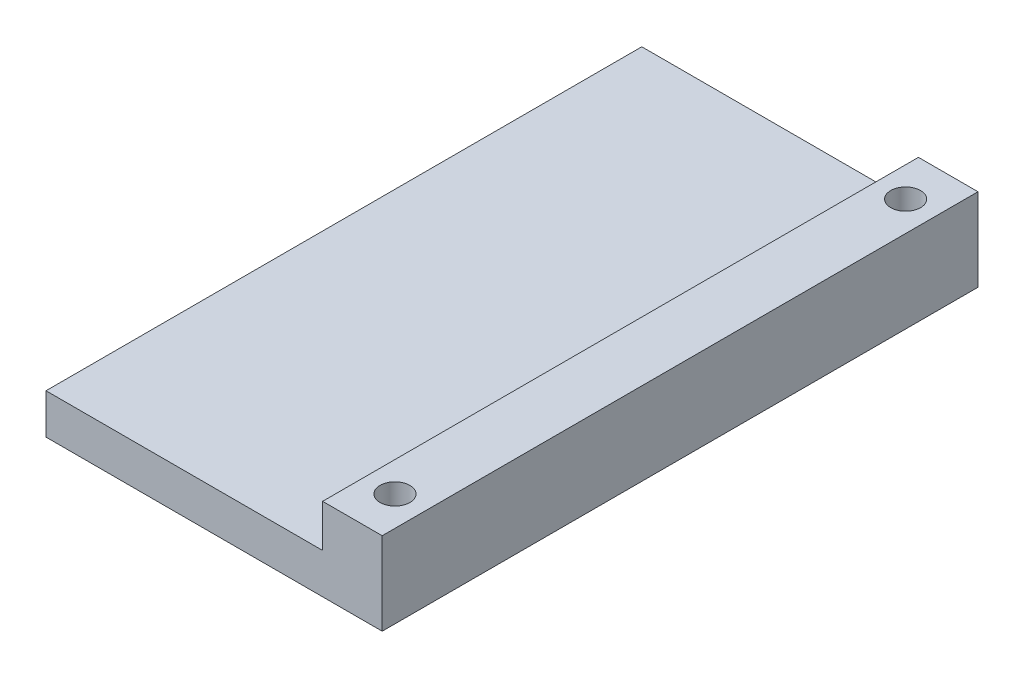
SolidWorks part; units mm, degrees
ref_plane "Front Plane" through (0, 0, 0) normal (0, 0, 1) x (1, 0, 0)
ref_plane "Top Plane" through (0, 0, 0) normal (0, 1, 0) x (1, 0, 0)
ref_plane "Right Plane" through (0, 0, 0) normal (1, 0, 0) x (0, 0, -1)
sketch "Sketch1" plane through (0, 0, 0) normal (0, 1, 0) x (1, 0, 0)
  line L1 (0, 0) -> (41.275, 0)
  line L2 (0, 0) -> (0, 88.9)
  line L3 (0, 88.9) -> (41.275, 88.9)
  line L4 (41.275, 0) -> (41.275, 88.9)
  line L5 (41.275, 88.9) -> (50.165, 88.9)
  line L6 (41.275, 88.9) -> (41.275, 0)
  line L7 (41.275, 0) -> (50.165, 0)
  line L8 (50.165, 88.9) -> (50.165, 0)
  dimension "D1" = 41.275
  dimension "D2" = 88.9
  dimension "D3" = 8.89
extrude "Boss-Extrude1" add sketch "Sketch1" along normal blind 5.9944 contours L1 L4 L3 L2 region at (20.6375, 0, -44.45)
extrude "Boss-Extrude2" add sketch "Sketch1<5>" along normal blind 12.3444 contours L8 L5 L4 L7 region at (45.72, 0, -44.45)
sketch "Sketch1<5>" plane through (0, 0, 0) normal (0, 1, 0) x (1, 0, 0) same geometry as "Sketch1"
sketch "Sketch3" plane through (0, 12.3444, 0) normal (0, 1, 0) x (1, 0, 0)
  line L0 (45.72, 82.55) -> (45.72, 6.35) construction
  line L1 (50.165, 88.9) -> (50.165, 0) construction
  line L2 (41.275, 88.9) -> (50.165, 88.9) construction
  line L3 (0, 0) -> (0, 88.9) construction
  circle A0 centre (45.72, 82.55) radius 2.2225
  circle A1 centre (45.72, 6.35) radius 2.2225
  point P4 (45.72, 44.45)
  point P6 (50.165, 44.45)
  point P7 (45.72, 88.9)
  dimension "D1" = 4.445
  dimension "D2" = 4.445
  dimension "D3" = 76.2
  dimension "D4" = 45.72
extrude "Cut-Extrude1" cut sketch "Sketch3" against normal through all both contours A1 | A0
sketch "Sketch4" plane through (0, 0, 0) normal (0, -1, 0) x (1, 0, 0)
  circle A0 centre (45.72, -6.35) radius 3.683
  circle A1 centre (45.72, -82.55) radius 3.683
  dimension "D1" = 7.366
  dimension "D2" = 7.366
extrude "Cut-Extrude2" cut sketch "Sketch4" against normal blind 4.064
